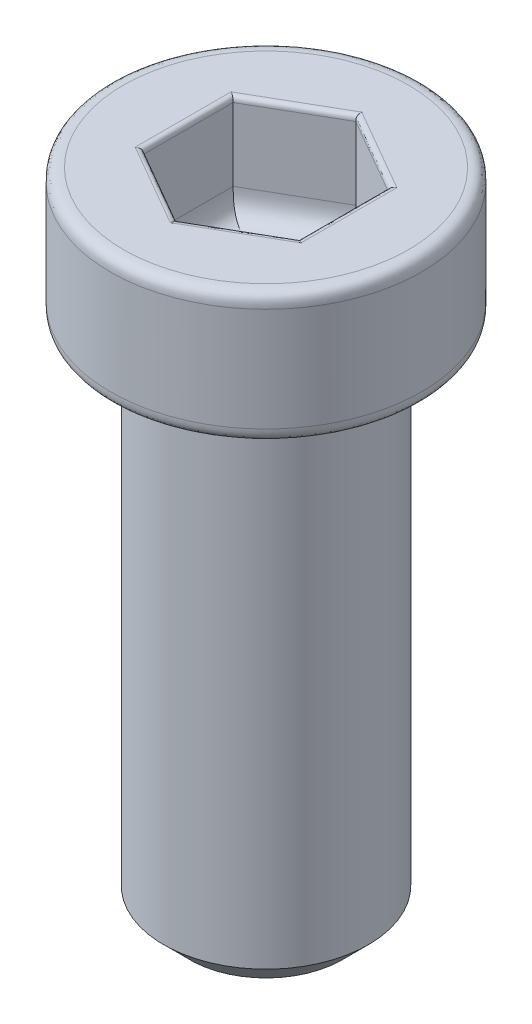
SolidWorks part; units mm, degrees
ref_plane "Front Plane" through (0, 0, 0) normal (0, 0, 1) x (1, 0, 0)
ref_plane "Top Plane" through (0, 0, 0) normal (0, 1, 0) x (1, 0, 0)
ref_plane "Right Plane" through (0, 0, 0) normal (1, 0, 0) x (0, 0, -1)
sketch "Sketch2" plane through (0, 0, 0) normal (1, 0, 0) x (0, 0, -1)
  line L0 (0, 0) -> (0, 25)
  line L1 (0, 25) -> (6, 25)
  line L2 (6, 25) -> (6, 20)
  line L3 (6, 20) -> (3.95, 20)
  line L4 (3.95, 20) -> (3.95, 0)
  line L5 (3.95, 0) -> (0, 0)
  dimension "D1" = 3.95
  dimension "D2" = 6
  dimension "D3" = 5
  dimension "D4" = 25
revolve "Revolve1" add sketch "Sketch2" angle 360 about L0
chamfer "Chamfer1" distance 1 angle 45 1 edges at (0, 0, -3.95)
sketch "Sketch3" plane through (0, 25, 0) normal (0, 1, 0) x (1, 0, 0)
  line L1 (0, 3.4641) -> (-3, 1.7321)
  line L2 (-3, 1.7321) -> (-3, -1.7321)
  line L3 (-3, -1.7321) -> (0, -3.4641)
  line L4 (0, -3.4641) -> (3, -1.7321)
  line L5 (3, -1.7321) -> (3, 1.7321)
  line L6 (3, 1.7321) -> (0, 3.4641)
  circle A0 centre (0, 0) radius 3 construction
  dimension "D1" = 6
extrude "Cut-Extrude1" cut sketch "Sketch3" against normal blind 4
fillet "Fillet1" radius 1 6 edges at (3, 21, 0) (1.5, 21, 2.5981) (-1.5, 21, 2.5981) (-3, 21, 0) (-1.5, 21, -2.5981) (1.5, 21, -2.5981) curvature continuous yes
fillet "Fillet2" radius 0.5 2 edges at (0, 20, -6) (0, 25, -6) curvature continuous yes
ref_axis "Axis1" through (0, 36, 0) along (0, -1, 0)
fillet "Fillet3" radius 0.2 6 edges at (-3, 25, 0) (-1.5, 25, 2.5981) (1.5, 25, 2.5981) (3, 25, 0) (1.5, 25, -2.5981) (-1.5, 25, -2.5981) curvature continuous yes
